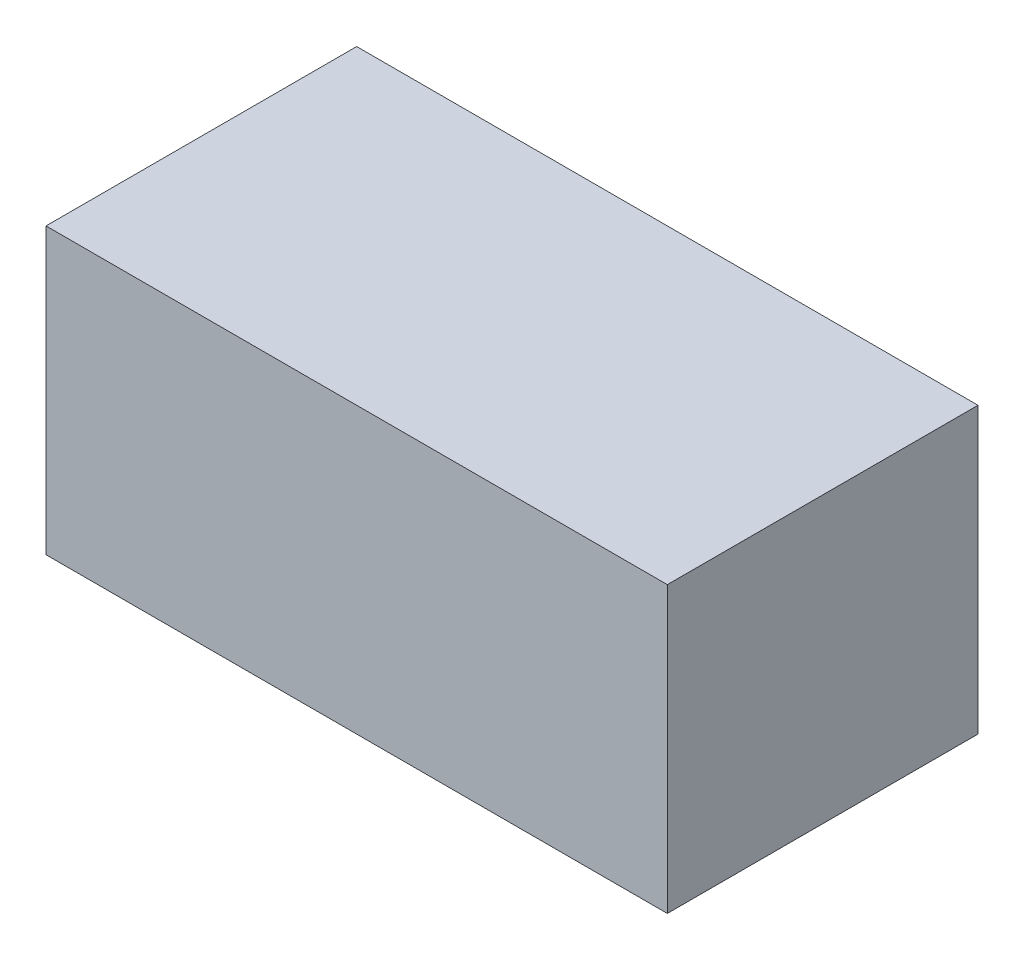
SolidWorks part; units mm, degrees
ref_plane "前基準面" through (0, 0, 0) normal (0, 0, 1) x (1, 0, 0)
ref_plane "上基準面" through (0, 0, 0) normal (0, 1, 0) x (1, 0, 0)
ref_plane "右基準面" through (0, 0, 0) normal (1, 0, 0) x (0, 0, -1)
sketch "草圖1" plane through (0, 0, 0) normal (0, 0, 1) x (1, 0, 0)
  line L0 (55, 0) -> (-55, 0) construction
  line L1 (-60, 27.5) -> (60, 27.5)
  line L2 (-60, 27.5) -> (-60, -27.5)
  line L3 (-60, -27.5) -> (60, -27.5)
  line L4 (60, 27.5) -> (60, -27.5)
  line L5 (0, -55) -> (0, 55) construction
  dimension "D1" = 120
  dimension "D2" = 55
  dimension "D3" = 27.5
  dimension "D4" = 60
extrude "填料-伸長1" add sketch "草圖1" along normal blind 60
